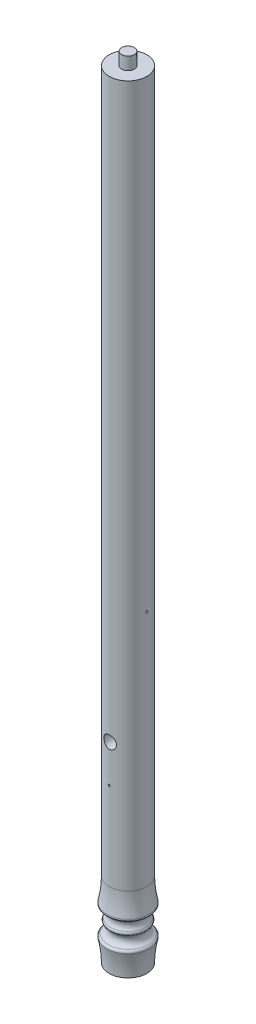
SolidWorks part; units mm, degrees
ref_plane "Front Plane" through (0, 0, 0) normal (0, 0, 1) x (1, 0, 0)
ref_plane "Top Plane" through (0, 0, 0) normal (0, 1, 0) x (1, 0, 0)
ref_plane "Right Plane" through (0, 0, 0) normal (1, 0, 0) x (0, 0, -1)
ref_plane "Plane3" through (0, 787.4, 0) normal (0, 1, 0) x (1, 0, 0)
ref_plane "Plane4" through (0, 800.1, 0) normal (0, 1, 0) x (1, 0, 0)
ref_plane "Plane5" through (0, 165.1, 0) normal (0, 1, 0) x (1, 0, 0)
ref_plane "Plane6" through (0, 203.2, 0) normal (0, 1, 0) x (1, 0, 0)
ref_plane "Plane7" through (0, 254, 0) normal (0, 1, 0) x (1, 0, 0)
ref_plane "Plane8" through (0, 25.4, 0) normal (0, 1, 0) x (1, 0, 0)
ref_plane "Plane9" through (0, 38.1, 0) normal (0, 1, 0) x (1, 0, 0)
ref_plane "Plane10" through (0, 50.8, 0) normal (0, 1, 0) x (1, 0, 0)
ref_plane "Plane11" through (0, 76.2, 0) normal (0, 1, 0) x (1, 0, 0)
ref_plane "Plane14" through (6.35, 0, 0) normal (1, 0, 0) x (0, 0, -1)
ref_plane "Plane15" through (15.875, 0, 0) normal (1, 0, 0) x (0, 0, -1)
ref_plane "Plane16" through (19.05, 0, 0) normal (1, 0, 0) x (0, 0, -1)
ref_plane "Plane17" through (22.225, 0, 0) normal (1, 0, 0) x (0, 0, -1)
sketch "center" plane through (0, 0, 0) normal (0, 0, 1) x (1, 0, 0)
  line L0 (0, 0) -> (0, 787.4)
  line L7 (154.1749, 787.4) -> (-154.1749, 787.4) construction
  line L13 (0, -76.5499) -> (0, 76.5499) construction
ref_axis "Axis1" through (0, -55, 0) along (0, 1, 0)
sketch "Sketch5" plane through (0, 25.4, 0) normal (0, 1, 0) x (1, 0, 0)
  line L0 (22.225, -76.5499) -> (22.225, 76.5499) construction
  circle A0 centre (0, 0) radius 22.225
ref_plane "Plane18" through (0, 31.75, 0) normal (0, 1, 0) x (1, 0, 0)
ref_plane "Plane19" through (0, 44.45, 0) normal (0, 1, 0) x (1, 0, 0)
sketch "Sketch6" plane through (0, 31.75, 0) normal (0, 1, 0) x (1, 0, 0)
  line L0 (15.875, -76.5499) -> (15.875, 76.5499) construction
  circle A0 centre (0, 0) radius 15.875
sketch "Sketch7" plane through (0, 38.1, 0) normal (0, 1, 0) x (1, 0, 0)
  circle A0 centre (0, 0) radius 18.9864
sketch "Sketch8" plane through (0, 44.45, 0) normal (0, 1, 0) x (1, 0, 0)
  circle A0 centre (0, 0) radius 15.875
sketch "Sketch9" plane through (0, 50.8, 0) normal (0, 1, 0) x (1, 0, 0)
  circle A0 centre (0, 0) radius 22.225
sketch "Sketch10" plane through (0, 76.2, 0) normal (0, 1, 0) x (1, 0, 0)
  circle A0 centre (0, 0) radius 18.9864
sketch "Sketch11" plane through (0, 0, 0) normal (0, 1, 0) x (1, 0, 0)
  circle A0 centre (0, 0) radius 18.9864
sketch "revolve sketch" plane through (0, 0, 0) normal (0, 0, 1) x (1, 0, 0)
  line L0 (0, 0) -> (19.05, 0)
  line L1 (18.9864, 0) -> (-18.9864, 0) construction
  line L2 (15.875, -76.5499) -> (15.875, 76.5499) construction
  line L3 (22.225, 25.4) -> (-22.225, 25.4) construction
  line L4 (22.225, -76.5499) -> (22.225, 76.5499) construction
  line L5 (154.1749, 25.4) -> (-154.1749, 25.4) construction
  line L6 (15.875, 31.75) -> (-15.875, 31.75) construction
  line L7 (154.1749, 31.75) -> (-154.1749, 31.75) construction
  line L8 (154.1749, 38.1) -> (-154.1749, 38.1) construction
  line L9 (15.875, 44.45) -> (-15.875, 44.45) construction
  line L10 (154.1749, 44.45) -> (-154.1749, 44.45) construction
  line L11 (22.225, 50.8) -> (-22.225, 50.8) construction
  line L12 (154.1749, 50.8) -> (-154.1749, 50.8) construction
  line L17 (19.05, -76.5499) -> (19.05, 76.5499) construction
  line L18 (154.1749, 0) -> (-154.1749, 0) construction
  line L19 (18.9864, 76.2) -> (-18.9864, 76.2) construction
  line L20 (154.1749, 76.2) -> (-154.1749, 76.2) construction
  line L21 (19.05, 76.2) -> (19.05, 787.4)
  line L22 (154.1749, 787.4) -> (-154.1749, 787.4) construction
  line L23 (19.05, 787.4) -> (6.35, 787.4)
  line L24 (6.35, -76.5499) -> (6.35, 76.5499) construction
  line L25 (6.35, 787.4) -> (6.35, 800.1)
  line L26 (152.7724, 800.1) -> (-152.7724, 800.1) construction
  line L27 (6.35, 800.1) -> (0, 800.1)
  line L28 (0, -76.5499) -> (0, 76.5499) construction
  line L29 (0, 800.1) -> (0, 0)
  arc A0 (19.05, 0) -> (21.6122, 22.8517) centre (122.2375, 0) cw
  arc A1 (15.875, 31.75) -> (20.018, 25.7959) centre (22.225, 31.75) ccw
  arc A2 (15.875, 31.75) -> (17.7809, 36.2857) centre (22.225, 31.75) cw
  arc A3 (17.7809, 39.9143) -> (15.875, 44.45) centre (22.225, 44.45) cw
  arc A4 (15.875, 44.45) -> (20.018, 50.4041) centre (22.225, 44.45) cw
  arc A5 (21.6122, 53.3483) -> (19.05, 76.2) centre (122.2375, 76.2) cw
  arc A6 (17.7809, 36.2857) -> (17.7809, 39.9143) centre (16.0033, 38.1) ccw
  arc A7 (21.6122, 22.8517) -> (20.018, 25.7959) centre (19.1352, 23.4142) ccw
  arc A8 (20.018, 50.4041) -> (21.6122, 53.3483) centre (19.1352, 52.7858) ccw
  point P49 (22.225, 38.1)
  point P52 (22.225, 25.4)
  point P55 (22.225, 50.8)
  point P60 (22.225, 25.4)
  point P62 (22.225, 50.8)
  dimension "D1" = 2.54
  dimension "D2" = 2.54
  dimension "D3" = 2.54
revolve "Revolve1" add sketch "revolve sketch" angle 360 about axis through (0, -55, 0) along (0, 1, 0)
ref_plane "Plane20" through (0, 317.5, 0) normal (0, 1, 0) x (1, 0, 0)
ref_axis "Axis2" through (162.1372, 317.5, 0) along (-1, 0, 0)
ref_axis "Axis3" through (0, 254, -88.99) along (0, 0, 1)
ref_axis "Axis4" through (0, 203.2, -88.99) along (0, 0, 1)
ref_axis "Axis5" through (0, 165.1, -88.99) along (0, 0, 1)
ref_plane "Plane21" through (0, 0, 6.35) normal (0, 0, 1) x (1, 0, 0)
ref_plane "Plane22" through (0, 0, 19.05) normal (0, 0, 1) x (1, 0, 0)
sketch "Sketch15" plane through (0, 0, 19.05) normal (0, 0, 1) x (1, 0, 0)
  line L0 (0, 0) -> (0, 787.4) construction
  line L1 (142.5044, 254) -> (-142.5044, 254) construction
  circle A0 centre (0, 254) radius 0.9922
  dimension "D1" = 1.9844
sketch "Sketch16" plane through (19.05, 0, 0) normal (1, 0, 0) x (0, 0, -1)
  line L0 (142.5044, 317.5) -> (-142.5044, 317.5) construction
  line L1 (0, 0) -> (0, 787.4) construction
  circle A0 centre (0, 317.5) radius 0.9922
  dimension "D1" = 1.9844
extrude "Cut-Extrude2" cut sketch "Sketch16" against normal up to surface (12.7 mm away) contours A0 up to plane "Plane14"
sketch "Sketch17" plane through (0, 0, 19.05) normal (0, 0, 1) x (1, 0, 0)
  line L0 (0, 0) -> (0, 787.4) construction
  line L1 (174.8529, 203.2) -> (-174.8529, 203.2) construction
  circle A0 centre (0, 203.2) radius 6.35
  dimension "D1" = 12.7
extrude "Cut-Extrude3" cut sketch "Sketch17" against normal up to surface (19.05 mm away) contours A0 up to plane "Front Plane"
sketch "Sketch18" plane through (0, 0, 19.05) normal (0, 0, 1) x (1, 0, 0)
  line L0 (172.3771, 165.1) -> (-172.3771, 165.1) construction
  circle A0 centre (0, 165.1) radius 0.9922
  dimension "D1" = 1.9844
extrude "Cut-Extrude4" cut sketch "Sketch18" against normal up to surface (12.7 mm away) up to plane "Plane21"
ref_plane "Plane23" through (0, 0, -19.05) normal (0, 0, -1) x (-1, 0, 0)
